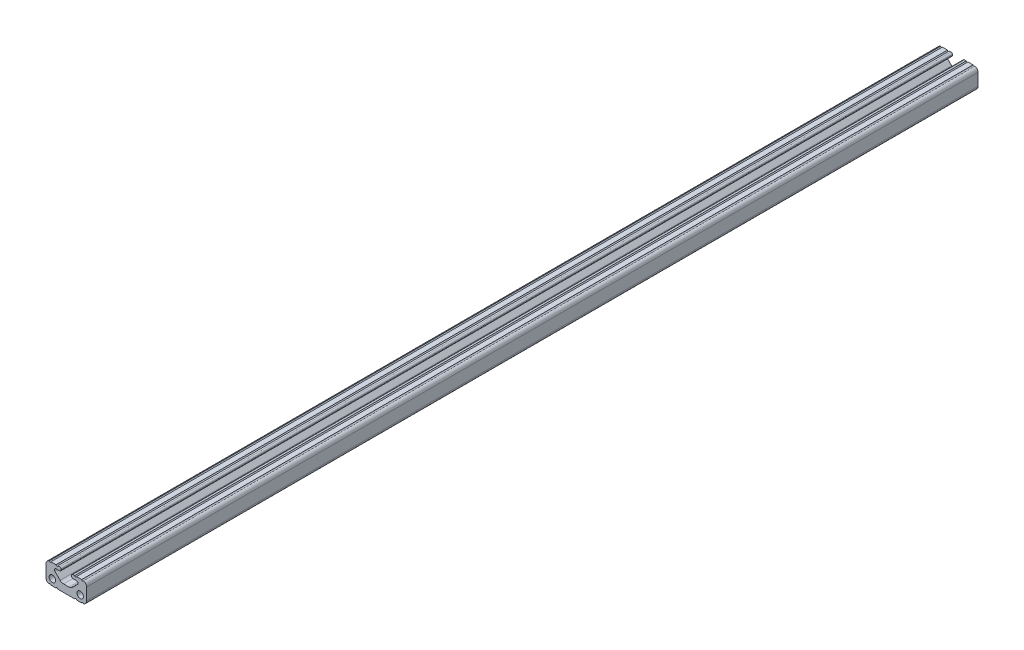
SolidWorks part; units mm, degrees
ref_plane "Front Plane" through (0, 0, 0) normal (0, 0, 1) x (1, 0, 0)
ref_plane "Top Plane" through (0, 0, 0) normal (0, 1, 0) x (1, 0, 0)
ref_plane "Right Plane" through (0, 0, 0) normal (1, 0, 0) x (0, 0, -1)
sketch "Sketch1" plane through (0, 0, 0) normal (0, 0, 1) x (1, 0, 0)
  line L0 (0, 6.35) -> (0, -6.35) construction
  line L1 (0, -6.35) -> (12.7, -6.35)
  line L2 (12.7, -6.35) -> (12.7, 6.35)
  line L3 (12.7, 6.35) -> (3.2512, 6.35)
  line L4 (3.2512, 6.35) -> (3.2512, 4.1402)
  line L5 (3.2512, 4.1402) -> (6.4224, 4.1402)
  line L6 (7.1255, 2.4426) -> (2.9811, -1.7018)
  line L7 (2.9811, -1.7018) -> (0, -1.7018)
  circle A0 centre (8.7249, -2.3876) radius 2.032
  arc A1 (6.4224, 4.1402) -> (7.1255, 2.4426) centre (6.4224, 3.1458) cw
  dimension "Center Hole Diameter" = 4.064
  dimension "D3" = 0.9944
  dimension "Rail Height" = 25.4
  dimension "Rail Width" = 12.7
  dimension "Hole CtoC" = 17.4498
  dimension "D1" = 3.9624
  dimension "T-Slot Width" = 6.5024
  dimension "Thickness" = 2.2098
  dimension "Inner Slot Width" = 14.8336
  dimension "Slot Depth" = 5.842
  dimension "D2" = 45
sketch "Sketch2" plane through (0, 0, 0) normal (1, 0, 0) x (0, 0, -1)
  line L0 (-304.8, -6.35) -> (304.8, -6.35) construction
  line L1 (-279.4, 0) -> (279.4, 0) construction
  dimension "Length" = 609.6
sketch "Sketch3" plane through (0, 0, 0) normal (0, 0, 1) x (1, 0, 0)
  line L0 (3.2512, 6.35) -> (3.2512, 4.1402) construction
  line L1 (12.7, 6.35) -> (3.2512, 6.35) construction
  line L2 (3.2512, 4.1402) -> (6.4224, 4.1402) construction
  line L3 (3.2512, 5.3556) -> (3.2512, 5.1346)
  line L4 (12.7, -6.35) -> (12.7, 6.35) construction
  line L5 (0, -6.35) -> (12.7, -6.35) construction
  line L6 (2.9811, -1.7018) -> (0, -1.7018) construction
  line L7 (7.1255, 2.4426) -> (2.9811, -1.7018) construction
  line L8 (0, -1.7018) -> (1.7454, -1.7018)
  line L9 (4.2456, 4.1402) -> (6.4224, 4.1402)
  line L10 (3.8549, -0.828) -> (7.1255, 2.4426)
  line L11 (0, -1.7018) -> (0, -6.35)
  line L12 (0, -6.35) -> (10.16, -6.35)
  line L13 (12.7, -3.81) -> (12.7, 3.81)
  line L14 (4.2456, 6.35) -> (10.16, 6.35)
  arc A0 (3.2512, 5.3556) -> (4.2456, 6.35) centre (4.2456, 5.3556) cw
  arc A1 (3.2512, 5.1346) -> (4.2456, 4.1402) centre (4.2456, 5.1346) ccw
  arc A2 (7.1255, 2.4426) -> (6.4224, 4.1402) centre (6.4224, 3.1458) ccw construction
  arc A3 (10.16, 6.35) -> (12.7, 3.81) centre (10.16, 3.81) cw
  arc A4 (10.16, -6.35) -> (12.7, -3.81) centre (10.16, -3.81) ccw
  arc A5 (7.1255, 2.4426) -> (6.4224, 4.1402) centre (6.4224, 3.1458) ccw
  circle A6 centre (8.7249, -2.3876) radius 2.032 construction
  circle A7 centre (8.7249, -2.3876) radius 2.032
  arc A8 (1.7454, -1.7018) -> (3.8549, -0.828) centre (1.7454, 1.2814) ccw
  dimension "D2" = 2.9832
extrude "Boss-Extrude1" add sketch "Sketch3" along normal mid plane 609.6
sketch "Sketch4" plane through (0, 0, 0) normal (0, 0, 1) x (1, 0, 0)
  line L0 (12.7, 6.35) -> (3.2512, 6.35) construction
  line L1 (0, -6.35) -> (12.7, -6.35) construction
  line L2 (10.7569, -2.3876) -> (10.7569, 6.35) construction
  line L3 (6.4224, 3.1458) -> (6.4224, 6.35) construction
  circle A0 centre (5.8699, 6.35) radius 0.5524
  circle A1 centre (10.2045, 6.35) radius 0.5524
  circle A2 centre (5.8699, -6.35) radius 0.5524
  circle A3 centre (10.2045, -6.35) radius 0.5524
  circle A4 centre (8.7249, -2.3876) radius 2.032 construction
  dimension "D1" = 1.1049
extrude "Cut-Extrude1" cut sketch "Sketch4" against normal through all both and the other way through all
mirror "Mirror1" about plane through (0, 0, 0) normal (1, 0, 0) of bodies 135
sketch "Sketch5" plane through (0, 0, 304.8) normal (0, 0, 1) x (1, 0, 0)
  line L16 (9.652, 6.35) -> (6.4224, 6.35)
  line L17 (5.3175, 6.35) -> (4.2456, 6.35)
  line L18 (3.2512, 5.3556) -> (3.2512, 5.1346)
  line L19 (4.2456, 4.1402) -> (6.4224, 4.1402)
  line L20 (7.1255, 2.4426) -> (3.8549, -0.828)
  line L21 (1.7454, -1.7018) -> (-1.7454, -1.7018)
  line L22 (-3.8549, -0.828) -> (-7.1255, 2.4426)
  line L23 (-6.4224, 4.1402) -> (-4.2456, 4.1402)
  line L24 (-3.2512, 5.1346) -> (-3.2512, 5.3556)
  line L25 (-4.2456, 6.35) -> (-5.3175, 6.35)
  line L26 (-6.4224, 6.35) -> (-9.652, 6.35)
  line L27 (-12.7, 3.81) -> (-12.7, -3.81)
  line L28 (-9.652, -6.35) -> (-6.4224, -6.35)
  line L29 (-5.3175, -6.35) -> (5.3175, -6.35)
  line L30 (6.4224, -6.35) -> (9.652, -6.35)
  line L31 (12.7, -3.81) -> (12.7, 3.81)
  line L32 (9.652, 6.35) -> (6.4224, 6.35)
  line L33 (5.3175, 6.35) -> (4.2456, 6.35)
  line L34 (3.2512, 5.3556) -> (3.2512, 5.1346)
  line L35 (4.2456, 4.1402) -> (6.4224, 4.1402)
  line L36 (7.1255, 2.4426) -> (3.8549, -0.828)
  line L37 (1.7454, -1.7018) -> (-1.7454, -1.7018)
  line L38 (-3.8549, -0.828) -> (-7.1255, 2.4426)
  line L39 (-6.4224, 4.1402) -> (-4.2456, 4.1402)
  line L40 (-3.2512, 5.1346) -> (-3.2512, 5.3556)
  line L41 (-4.2456, 6.35) -> (-5.3175, 6.35)
  line L42 (-6.4224, 6.35) -> (-9.652, 6.35)
  line L43 (-12.7, 3.81) -> (-12.7, -3.81)
  line L44 (-9.652, -6.35) -> (-6.4224, -6.35)
  line L45 (-5.3175, -6.35) -> (5.3175, -6.35)
  line L46 (6.4224, -6.35) -> (9.652, -6.35)
  line L47 (12.7, -3.81) -> (12.7, 3.81)
  arc A20 (12.7, 3.81) -> (10.7524, 6.2799) centre (10.16, 3.81) ccw
  arc A21 (9.652, 6.35) -> (10.7524, 6.2799) centre (10.2045, 6.35) ccw
  arc A22 (5.3175, 6.35) -> (6.4224, 6.35) centre (5.8699, 6.35) ccw
  arc A23 (4.2456, 6.35) -> (3.2512, 5.3556) centre (4.2456, 5.3556) ccw
  arc A24 (3.2512, 5.1346) -> (4.2456, 4.1402) centre (4.2456, 5.1346) ccw
  arc A25 (7.1255, 2.4426) -> (6.4224, 4.1402) centre (6.4224, 3.1458) ccw
  arc A26 (1.7454, -1.7018) -> (3.8549, -0.828) centre (1.7454, 1.2814) ccw
  arc A27 (-3.8549, -0.828) -> (-1.7454, -1.7018) centre (-1.7454, 1.2814) ccw
  arc A28 (-6.4224, 4.1402) -> (-7.1255, 2.4426) centre (-6.4224, 3.1458) ccw
  arc A29 (-4.2456, 4.1402) -> (-3.2512, 5.1346) centre (-4.2456, 5.1346) ccw
  arc A30 (-3.2512, 5.3556) -> (-4.2456, 6.35) centre (-4.2456, 5.3556) ccw
  arc A31 (-6.4224, 6.35) -> (-5.3175, 6.35) centre (-5.8699, 6.35) ccw
  arc A32 (-10.7524, 6.2799) -> (-9.652, 6.35) centre (-10.2045, 6.35) ccw
  arc A33 (-10.7524, 6.2799) -> (-12.7, 3.81) centre (-10.16, 3.81) ccw
  arc A34 (-12.7, -3.81) -> (-10.7524, -6.2799) centre (-10.16, -3.81) ccw
  arc A35 (-9.652, -6.35) -> (-10.7524, -6.2799) centre (-10.2045, -6.35) ccw
  arc A36 (-5.3175, -6.35) -> (-6.4224, -6.35) centre (-5.8699, -6.35) ccw
  arc A37 (6.4224, -6.35) -> (5.3175, -6.35) centre (5.8699, -6.35) ccw
  arc A38 (10.7524, -6.2799) -> (9.652, -6.35) centre (10.2045, -6.35) ccw
  arc A39 (10.7524, -6.2799) -> (12.7, -3.81) centre (10.16, -3.81) ccw
  arc A40 (12.7, 3.81) -> (10.7524, 6.2799) centre (10.16, 3.81) ccw
  arc A41 (9.652, 6.35) -> (10.7524, 6.2799) centre (10.2045, 6.35) ccw
  arc A42 (5.3175, 6.35) -> (6.4224, 6.35) centre (5.8699, 6.35) ccw
  arc A43 (4.2456, 6.35) -> (3.2512, 5.3556) centre (4.2456, 5.3556) ccw
  arc A44 (3.2512, 5.1346) -> (4.2456, 4.1402) centre (4.2456, 5.1346) ccw
  arc A45 (7.1255, 2.4426) -> (6.4224, 4.1402) centre (6.4224, 3.1458) ccw
  arc A46 (1.7454, -1.7018) -> (3.8549, -0.828) centre (1.7454, 1.2814) ccw
  arc A47 (-3.8549, -0.828) -> (-1.7454, -1.7018) centre (-1.7454, 1.2814) ccw
  arc A48 (-6.4224, 4.1402) -> (-7.1255, 2.4426) centre (-6.4224, 3.1458) ccw
  arc A49 (-4.2456, 4.1402) -> (-3.2512, 5.1346) centre (-4.2456, 5.1346) ccw
  arc A50 (-3.2512, 5.3556) -> (-4.2456, 6.35) centre (-4.2456, 5.3556) ccw
  arc A51 (-6.4224, 6.35) -> (-5.3175, 6.35) centre (-5.8699, 6.35) ccw
  arc A52 (-10.7524, 6.2799) -> (-9.652, 6.35) centre (-10.2045, 6.35) ccw
  arc A53 (-10.7524, 6.2799) -> (-12.7, 3.81) centre (-10.16, 3.81) ccw
  arc A54 (-12.7, -3.81) -> (-10.7524, -6.2799) centre (-10.16, -3.81) ccw
  arc A55 (-9.652, -6.35) -> (-10.7524, -6.2799) centre (-10.2045, -6.35) ccw
  arc A56 (-5.3175, -6.35) -> (-6.4224, -6.35) centre (-5.8699, -6.35) ccw
  arc A57 (6.4224, -6.35) -> (5.3175, -6.35) centre (5.8699, -6.35) ccw
  arc A58 (10.7524, -6.2799) -> (9.652, -6.35) centre (10.2045, -6.35) ccw
  arc A59 (10.7524, -6.2799) -> (12.7, -3.81) centre (10.16, -3.81) ccw
  dimension "D1" = 0
extrude "Cut-Extrude2" cut sketch "Sketch5" against normal offset from surface (50.8 mm away) 558.8 up to face at (0, 1.3921, -304.8)
equation "\"D3@Sketch1\"=\"Thickness@Sketch1\"*0.45"
equation "\"D1@Sketch3\"=\"Rail Width@Sketch1\"*0.2"
equation "\"D2@Sketch3\"=\"D3@Sketch1\"*3"
equation "\"D1@Boss-Extrude1\"=\"length@sketch2\""
equation "\"D1@Sketch4\"=\"Thickness@Sketch1\"*0.5"
